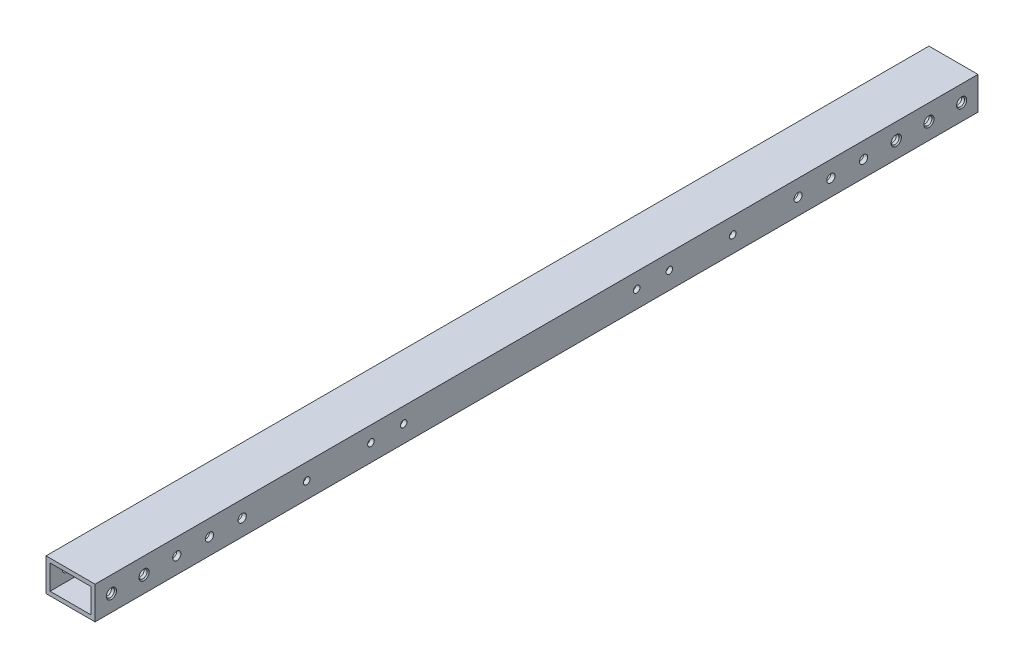
SolidWorks part; units mm, degrees
ref_plane "Front Plane" through (0, 0, 0) normal (0, 0, 1) x (1, 0, 0)
ref_plane "Top Plane" through (0, 0, 0) normal (0, 1, 0) x (1, 0, 0)
ref_plane "Right Plane" through (0, 0, 0) normal (1, 0, 0) x (0, 0, -1)
sketch "Sketch1" plane through (0, 0, 0) normal (0, 0, 1) x (1, 0, 0)
  line L0 (-15.875, 9.525) -> (15.875, 9.525)
  line L2 (-19.05, 12.7) -> (19.05, 12.7)
  line L3 (-19.05, 12.7) -> (-19.05, -12.7)
  line L4 (-19.05, -12.7) -> (19.05, -12.7)
  line L5 (19.05, 12.7) -> (19.05, -12.7)
  line L10 (15.875, 9.525) -> (15.875, -9.525)
  line L11 (-15.875, -9.525) -> (15.875, -9.525)
  line L12 (-15.875, 9.525) -> (-15.875, -9.525)
  point P12 (0, 12.7)
  point P14 (19.05, 0)
  dimension "Wall Thickness" = 3.175
  dimension "Outside Width" = 38.1
  dimension "Outside Height" = 25.4
  dimension "Inside Height" = 19.05
  dimension "Inside Width" = 31.75
sketch "Sketch2" plane through (0, 0, 0) normal (1, 0, 0) x (0, 0, -1)
  line L0 (342.9, 0) -> (-342.9, 0)
  point P4 (0, 0)
  point P7 (-342.9, 0)
  point P10 (342.9, 0)
  dimension "Length" = 685.8
sketch "Sketch3" plane through (0, 0, 0) normal (0, 0, 1) x (1, 0, 0)
  line L21 (19.05, 12.7) -> (-19.05, 12.7)
  line L22 (19.05, -12.7) -> (19.05, 12.7)
  line L23 (-19.05, -12.7) -> (19.05, -12.7)
  line L24 (-19.05, 12.7) -> (-19.05, -12.7)
  line L25 (19.05, 12.7) -> (-19.05, 12.7)
  line L26 (19.05, -12.7) -> (19.05, 12.7)
  line L27 (-19.05, -12.7) -> (19.05, -12.7)
  line L28 (-19.05, 12.7) -> (-19.05, -12.7)
  line L29 (15.875, 9.525) -> (-15.875, 9.525)
  line L30 (15.875, -9.525) -> (15.875, 9.525)
  line L31 (-15.875, -9.525) -> (15.875, -9.525)
  line L32 (-15.875, 9.525) -> (-15.875, -9.525)
  line L33 (15.875, 9.525) -> (-15.875, 9.525)
  line L34 (15.875, -9.525) -> (15.875, 9.525)
  line L35 (-15.875, -9.525) -> (15.875, -9.525)
  line L36 (-15.875, 9.525) -> (-15.875, -9.525)
  dimension "D1" = 0
  dimension "D2" = 0
extrude "Boss-Extrude1" add sketch "Sketch3" along normal up to vertex (342.9 mm away) and the other way up to vertex (342.9 mm away) up to point (0, 0, 342.9) other way up to point (0, 0, -342.9)
sketch "Drawing Reference" plane through (0, 0, 0) normal (1, 0, 0) x (0, 0, -1)
  line L0 (-342.9, 0) -> (342.9, 0) construction
  line L1 (0, -12.7) -> (0, 12.7) construction
  line L2 (-342.9, -12.7) -> (342.9, -12.7) construction
  line L5 (-342.9, 12.7) -> (342.9, 12.7) construction
  point P7 (-315.468, 0)
  point P8 (315.468, 0)
  dimension "D1" = 27.432
sketch "Sketch4" plane through (-19.05, 0, 0) normal (-1, 0, 0) x (0, 0, 1)
  line L0 (-342.9, 0) -> (-330.2, 0)
  line L1 (-342.9, 12.7) -> (-342.9, -12.7) construction
  line L2 (-330.2, 0) -> (-304.8, 0)
  line L3 (-304.8, 0) -> (-279.4, 0)
  line L4 (-279.4, 0) -> (-254, 0)
  line L5 (-254, 0) -> (-228.6, 0)
  line L6 (-228.6, 0) -> (-203.2, 0)
  line L7 (342.9, 0) -> (330.2, 0)
  line L8 (342.9, 12.7) -> (342.9, -12.7) construction
  line L9 (330.2, 0) -> (304.8, 0)
  line L10 (304.8, 0) -> (279.4, 0)
  line L11 (279.4, 0) -> (254, 0)
  line L12 (254, 0) -> (228.6, 0)
hole_wizard "1/4 (0.25) Diameter Hole2" positions "Sketch7" profile "Sketch8" hole size "1/4" standard "ANSI Inch" end condition through all
sketch "Sketch7" plane through (-19.05, 0, 0) normal (-1, 0, 0) x (0, 0, 1)
  point P0 (-330.2, 0)
  point P3 (-304.8, 0)
  point P7 (330.2, 0)
  point P11 (-279.4, 0)
  point P14 (304.8, 0)
sketch "Sketch8" plane through (-19.05, 0, -330.2) normal (0, 1, 0) x (0, 0, 1)
  line L0 (0, 0) -> (0, 38.1)
  line L1 (0, 38.1) -> (3.9624, 38.1)
  line L2 (3.175, 37.1942) -> (3.175, 0)
  line L5 (3.175, 0) -> (0, 0)
  line L7 (3.9624, 38.1) -> (3.175, 37.1942)
  line L8 (-3.9624, 38.1) -> (-3.175, 37.1942) construction
  line L11 (0, -6.35) -> (0, 107.95) construction
  dimension "Thru Hole Dia." = 6.35
  dimension "Thru Hole Depth" = 38.1
  dimension "Far C'Sink Dia." = 7.9248
  dimension "Far C'Sink Angle" = 82
hole_wizard "1/4 (0.25) Diameter Hole3" positions "Sketch9" profile "Sketch10" hole size "1/4" standard "ANSI Inch" end condition through all
sketch "Sketch9" plane through (19.05, 0, 0) normal (1, 0, 0) x (0, 0, -1)
  point P0 (-279.4, 0)
  point P3 (-254, 0)
  point P6 (-228.6, 0)
  point P9 (254, 0)
  point P12 (228.6, 0)
  point P15 (203.2, 0)
sketch "Sketch10" plane through (19.05, 0, 279.4) normal (0, 1, 0) x (0, 0, -1)
  line L0 (0, 0) -> (0, 38.1)
  line L1 (0, 38.1) -> (3.175, 38.1)
  line L2 (3.175, 38.1) -> (3.175, 0)
  line L5 (3.175, 0) -> (0, 0)
  line L11 (0, -6.35) -> (0, 107.95) construction
  dimension "Thru Hole Dia." = 6.35
  dimension "Thru Hole Depth" = 38.1
hole_wizard "13/64 (0.20313) Diameter Hole1" positions "Sketch11" profile "Sketch12" hole size "13/64" standard "ANSI Inch" end condition through all
sketch "Sketch11" plane through (19.05, 0, 0) normal (1, 0, 0) x (0, 0, -1)
  point P0 (152.4, 0)
  point P3 (-178.5118, 0)
sketch "Sketch12" plane through (19.05, 0, -152.4) normal (0, 1, 0) x (0, 0, -1)
  line L0 (0, 0) -> (0, 38.1)
  line L1 (0, 38.1) -> (2.5798, 38.1)
  line L2 (2.5798, 38.1) -> (2.5798, 0)
  line L5 (2.5798, 0) -> (0, 0)
  line L11 (0, -6.35) -> (0, 107.95) construction
  dimension "Thru Hole Dia." = 5.1595
  dimension "Thru Hole Depth" = 38.1
sketch "Sketch13" plane through (19.05, 0, 0) normal (1, 0, 0) x (0, 0, -1)
  line L0 (-103.5434, 0.3445) -> (-128.9434, 0.3445)
  line L1 (77.7875, 0.7112) -> (102.8316, 0.7112)
hole_wizard "#10 Clearance Hole1" positions "Sketch14" profile "Sketch15" hole size "#10" standard "ANSI Inch" end condition through all
sketch "Sketch14" plane through (19.05, 0, 0) normal (1, 0, 0) x (0, 0, -1)
  point P19 (-128.5875, 0.7112)
  point P22 (-103.1875, 0.7112)
  point P35 (77.7875, 0.7112)
  point P38 (103.1875, 0.7112)
sketch "Sketch15" plane through (19.05, 0.7112, 128.5875) normal (0, 1, 0) x (0, 0, -1)
  line L0 (0, 0) -> (0, 38.1)
  line L1 (0, 38.1) -> (2.5527, 38.1)
  line L2 (2.5527, 38.1) -> (2.5527, 0)
  line L5 (2.5527, 0) -> (0, 0)
  line L11 (0, -6.35) -> (0, 107.95) construction
  dimension "Thru Hole Dia." = 5.1054
  dimension "Thru Hole Depth" = 38.1
equation "\"D1@Drawing Reference\"=\"Outside Width@Sketch1\" * 0.72"
